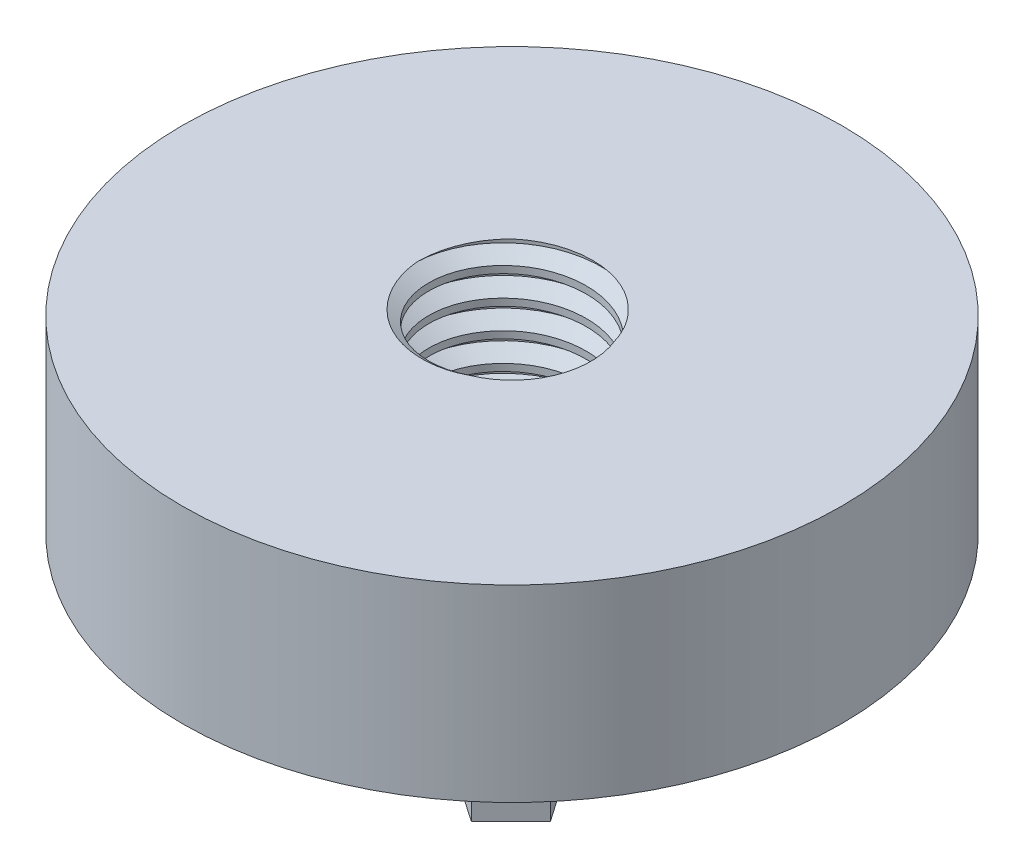
SolidWorks part; units mm, degrees
ref_plane "Alzado" through (0, 0, 0) normal (0, 0, 1) x (1, 0, 0)
ref_plane "Planta" through (0, 0, 0) normal (0, 1, 0) x (1, 0, 0)
ref_plane "Vista lateral" through (0, 0, 0) normal (1, 0, 0) x (0, 0, -1)
sketch "Croquis1" plane through (0, 0, 0) normal (0, 0, 1) x (1, 0, 0)
  line L0 (5, 0) -> (-7.5, 0)
  line L1 (-7.5, 0) -> (-7.5, -5)
  line L3 (-7.5, -5) -> (-7.5, -10)
  line L4 (-7.5, -10) -> (10, -10)
  line L5 (10, -10) -> (10, -8)
  line L6 (5, 0) -> (5, -8)
  line L7 (5, -8) -> (10, -8)
  dimension "D1" = 8
  dimension "D2" = 5
  dimension "D3" = 17.5
  dimension "D4" = 5
  dimension "D5" = 5
revolve "Revolución1" add sketch "Croquis1" angle 360 about L5
thread "Rosca1" pitch 1.5 method extrude profile "Perfil de rosca1" start angle 0, offset 1.5, length 0, pitch 1.5, diameter 10
ref_plane "Plano1" through (5, 1.5, 0) normal (0, 0, 1) x (-1, 0, 0)
sketch "Perfil de rosca1" plane through (5, 1.5, 0) normal (0, 0, 1) x (-1, 0, 0)
  line L0 (0, 0) -> (0, 1.5) construction
  line L11 (0, 0) -> (0, 1.3125)
  line L12 (0, 1.3125) -> (-0.8119, 0.8437)
  line L13 (-0.8119, 0.8437) -> (-0.8119, 0.4687)
  line L15 (-0.8119, 0.4687) -> (0, 0)
  line L17 (-0.8119, 0.6562) -> (0, 0.6562) construction
  point P2 (0, 0)
  dimension "Pitch" = 1.5
  dimension "Profile_Angle" = 60
  dimension "Profile_Land" = 0.375
  dimension "Profile_Height" = 0.8119
sketch "Croquis5" plane through (0, 0, 0) normal (0, 1, 0) x (1, 0, 0)
  circle A0 centre (10, 0) radius 17.5
  circle A1 centre (10, 0) radius 17.5 construction
  point P3 (0, 0)
extrude "Cortar-Extruir1" cut sketch "Croquis5" along normal blind 10
sketch "Croquis4" plane through (0, -10, 0) normal (0, -1, 0) x (1, 0, 0)
  line L0 (-141.5039, -246.875) -> (-141.5039, -34.875) construction
  line L1 (-138.3656, -237.2134) -> (-138.3656, -25.2134) construction
  line L3 (82.7289, 243.5082) -> (424.0622, 243.5082) construction
  line L4 (10.0713, 2.3632) -> (16.432, 8.724)
  line L5 (16.432, 8.724) -> (16.9315, 10.1092)
  line L6 (16.9315, 10.1092) -> (20.1542, 12.3143)
  line L7 (20.1542, 12.3143) -> (22.2556, 10.2129)
  line L8 (22.2556, 10.2129) -> (20.0412, 7.0183)
  line L9 (20.0412, 7.0183) -> (18.5994, 6.5566)
  line L10 (18.5994, 6.5566) -> (12.2387, 0.1959)
  line L11 (12.2387, 0.1959) -> (13.7747, -1.3401)
  line L12 (13.7747, -1.3401) -> (12.1067, -3.0081)
  line L13 (12.1067, -3.0081) -> (10.4328, -3.5442)
  line L14 (10.4328, -3.5442) -> (9.8442, -5.1766)
  line L15 (9.8442, -5.1766) -> (3.2961, -11.7248)
  line L16 (10.0713, 2.3632) -> (8.639, 3.7956)
  line L17 (8.639, 3.7956) -> (6.971, 2.1276)
  line L18 (6.971, 2.1276) -> (6.4208, 0.6016)
  line L19 (6.4208, 0.6016) -> (4.8189, -0.1513)
  line L20 (4.8189, -0.1513) -> (-1.7927, -6.636)
  line L21 (0.1391, -7.9459) -> (5.6895, -2.3955)
  line L22 (1.8353, -9.9436) -> (7.6212, -4.1577)
  line L23 (14.592, 8.4075) -> (9.7731, 13.2264) construction
  arc A1 (3.2961, -11.7248) -> (-1.7927, -6.636) centre (1.0191, -8.913) cw
  arc A2 (1.8353, -9.9436) -> (0.1391, -7.9459) centre (1.1956, -8.7678) cw
  arc A3 (7.6212, -4.1577) -> (5.6895, -2.3955) centre (6.5247, -3.4199) ccw
  text T0 "<b>III</b>" font "Constantia" height 4
extrude "Saliente-Extruir1" add sketch "Croquis4" along normal blind 2
